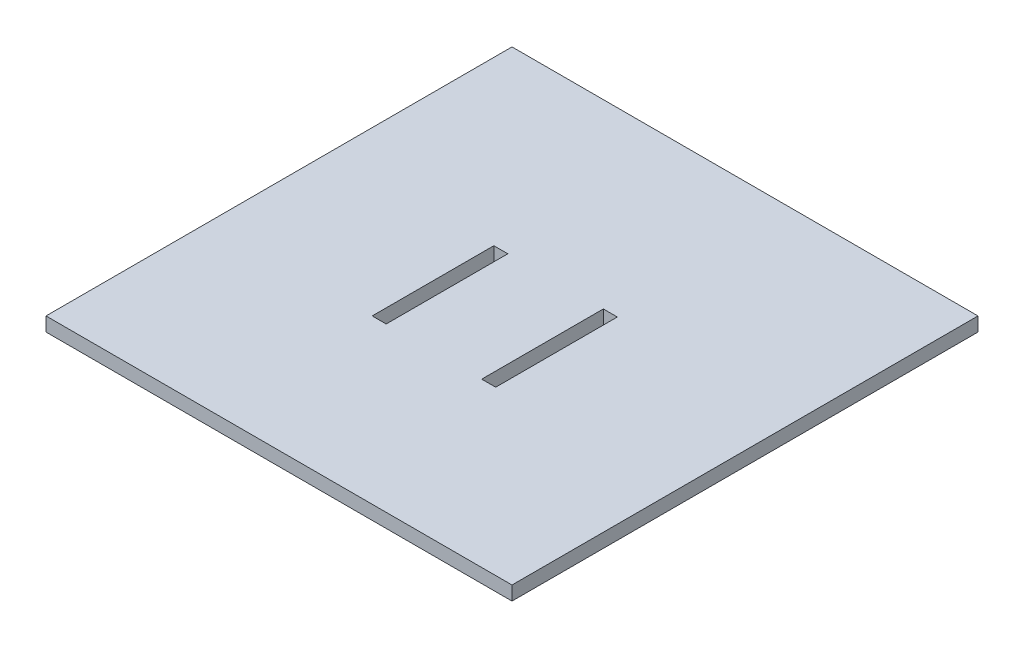
SolidWorks part; units mm, degrees
ref_plane "Plano frontal" through (0, 0, 0) normal (0, 0, 1) x (1, 0, 0)
ref_plane "Plano superior" through (0, 0, 0) normal (0, 1, 0) x (1, 0, 0)
ref_plane "Plano direito" through (0, 0, 0) normal (1, 0, 0) x (0, 0, -1)
sketch "BaixoBaseEsb" plane through (0, 0, 0) normal (0, 1, 0) x (1, 0, 0)
  line L1 (0, 0) -> (100, 0)
  line L2 (0, 0) -> (0, 100)
  line L3 (0, 100) -> (100, 100)
  line L4 (100, 0) -> (100, 100)
  line L5 (35, 61.1) -> (38, 61.1)
  line L6 (35, 61.1) -> (35, 35)
  line L7 (35, 35) -> (38, 35)
  line L8 (38, 61.1) -> (38, 35)
  line L9 (58.5, 61.1) -> (61.5, 61.1)
  line L10 (58.5, 61.1) -> (58.5, 35)
  line L11 (58.5, 35) -> (61.5, 35)
  line L12 (61.5, 61.1) -> (61.5, 35)
  dimension "D1" = 100
  dimension "D2" = 100
  dimension "D3" = 26.1
  dimension "D4" = 3
  dimension "D5" = 20.5
  dimension "D6" = 3
  dimension "D7" = 35
  dimension "D8" = 35
extrude "Ressalto-extrusão1" add sketch "BaixoBaseEsb" along normal blind 3
